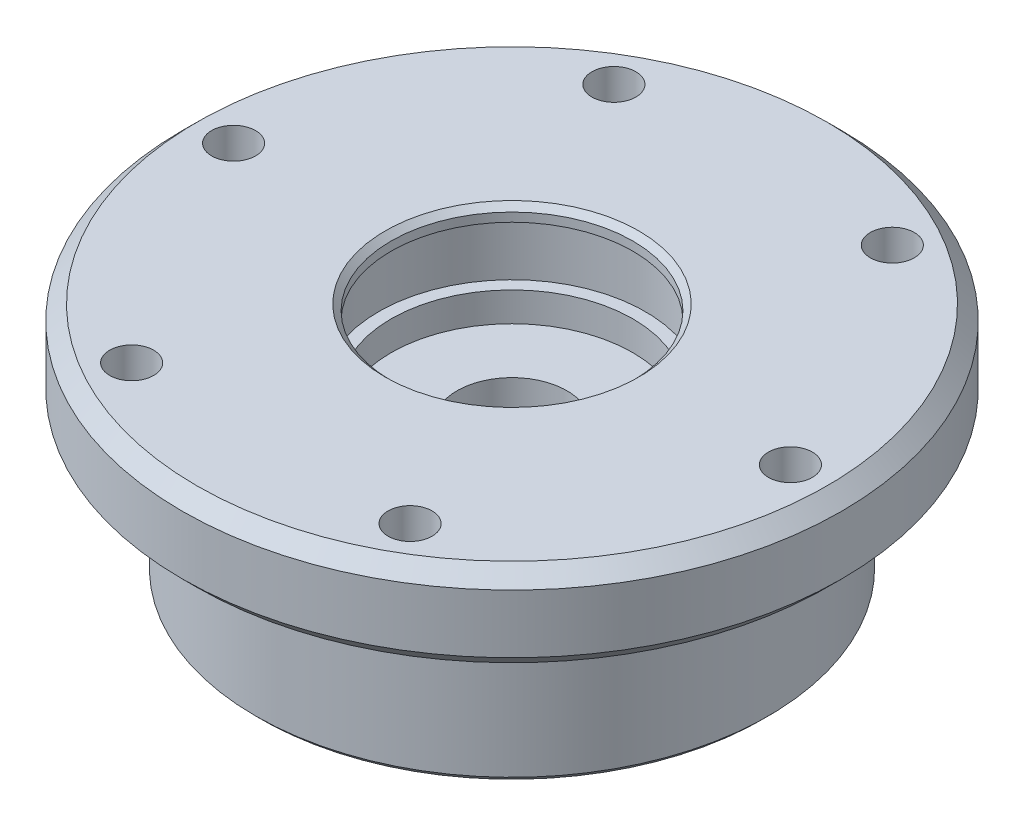
SolidWorks part; units mm, degrees
ref_plane "Front Plane" through (0, 0, 0) normal (0, 0, 1) x (1, 0, 0)
ref_plane "Top Plane" through (0, 0, 0) normal (0, 1, 0) x (1, 0, 0)
ref_plane "Right Plane" through (0, 0, 0) normal (1, 0, 0) x (0, 0, -1)
sketch "Sketch1" plane through (0, 0, 0) normal (0, 1, 0) x (1, 0, 0)
  circle A0 centre (0, 0) radius 19 construction
  circle A1 centre (19, 0) radius 1.5
  circle A2 centre (9.5, -16.4545) radius 1.5
  circle A3 centre (-9.5, -16.4545) radius 1.5
  circle A4 centre (-19, 0) radius 1.5
  circle A5 centre (-9.5, 16.4545) radius 1.5
  circle A6 centre (9.5, 16.4545) radius 1.5
  circle A7 centre (0, 0) radius 22.5
  circle A8 centre (0, 0) radius 8.25
  point P17 (0, 0)
  dimension "D1" = 38
  dimension "D2" = 3
  dimension "D5" = 16.5
  dimension "D4" = 3.5
  dimension "D3" = 6
extrude "Boss-Extrude1" add sketch "Sketch1" along normal mid plane 6
sketch "Sketch2" plane through (0, 0, 0) normal (0, 1, 0) x (1, 0, 0)
  circle A0 centre (0, 0) radius 9.1
  dimension "D1" = 18.2
extrude "Cut-Extrude1" cut sketch "Sketch2" against normal mid plane 4
sketch "Sketch3" plane through (0, -3, 0) normal (0, 1, 0) x (1, 0, 0)
  circle A0 centre (0, 0) radius 17.5
  circle A1 centre (0, 0) radius 20.5
  circle A2 centre (9.5, 16.4545) radius 1.5 construction
extrude "Boss-Extrude2" add sketch "Sketch3" along normal blind 1
sketch "Sketch4" plane through (0, -3, 0) normal (0, -1, 0) x (1, 0, 0)
  circle A0 centre (0, 0) radius 17.5
  circle A2 centre (0, 0) radius 3.75
  dimension "D1" = 35
  dimension "D2" = 7.5
extrude "Boss-Extrude3" add sketch "Sketch4" along normal blind 10
sketch "Sketch5" plane through (0, -3, 0) normal (0, -1, 0) x (1, 0, 0)
  circle A0 centre (0, 0) radius 19
  circle A1 centre (0, 0) radius 17.5 construction
  circle A2 centre (0, 0) radius 17.5
  dimension "D1" = 1.5
extrude "Boss-Extrude4" add sketch "Sketch5" along normal blind 0.5
chamfer "Chamfer1" distance 1 angle 45 2 edges at (0, -3, 22.5) (0, 3, 22.5)
chamfer "Chamfer2" [suppressed] distance 0.4 angle 45
chamfer "Chamfer3" distance 0.4 angle 45 1 edges at (0, 3, 8.25)
sketch "Sketch6" plane through (0, -13, 0) normal (0, -1, 0) x (1, 0, 0)
  circle A0 centre (0, 0) radius 7.5 construction
  circle A1 centre (7.5, 0) radius 2.35
  circle A2 centre (0, 7.5) radius 2.35
  circle A3 centre (-7.5, 0) radius 2.35
  circle A4 centre (0, -7.5) radius 2.35
  dimension "D1" = 15
  dimension "D2" = 4.7
extrude "Cut-Extrude2" cut sketch "Sketch6" against normal blind 4
sketch "Sketch7" plane through (0, -13, 0) normal (0, -1, 0) x (1, 0, 0)
  circle A0 centre (0, 7.5) radius 1.75
  circle A1 centre (7.5, 0) radius 1.75
  circle A2 centre (0, -7.5) radius 1.75
  circle A3 centre (-7.5, 0) radius 1.75
  dimension "D1" = 3.5
extrude "Cut-Extrude3" cut sketch "Sketch7" against normal blind 8
chamfer "Chamfer4" distance 0.4 angle 45 1 edges at (0, -13, -17.5)
sketch "Sketch8" plane through (0, -3, 0) normal (0, 1, 0) x (1, 0, 0)
  circle A0 centre (0, 0) radius 8.25 construction
  circle A1 centre (0, 0) radius 8.25
extrude "Cut-Extrude4" cut sketch "Sketch8" against normal blind 1
equation "\"RotorRadius\"= 25mm"
equation "\"Eccentricity\"= 1.00mm"
equation "\"RollerRadius\"= 1.5mm"
equation "\"GearRatio\"= 20"
equation "\"RollerCount\"=\"GearRatio\" + 1"
equation "\"RotorThickness\"= 6mm"
equation "\"OutputRollerRadius\"= 1.5mm"
equation "\"OutputRollerCount\"= 6"
equation "\"OutputRollerHoleCircleRadius\"=\"RotorRadius\"- 4 * \"OutputRollerRadius\""
equation "\"RotorGap\"= 0.5mm"
equation "\"D1@Sketch1\"=2*\"OutputRollerHoleCircleRadius\""
equation "\"D2@Sketch1\"=\"OutputRollerRadius\"*2"
equation "\"D1@Boss-Extrude1\"=\"RotorThickness\""
